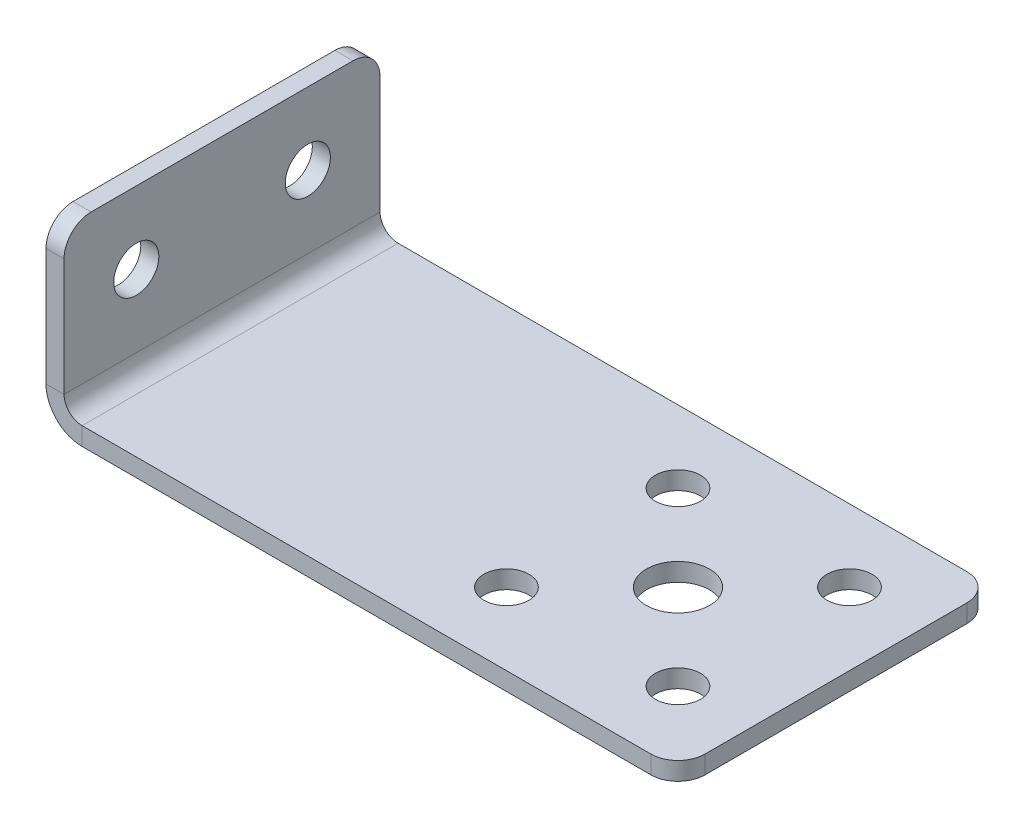
SolidWorks part; units mm, degrees
note: The reader was unsure of these and kept them because the rebuilt part matched: flange length of "Edge-Flange1".
ref_plane "Front Plane" through (0, 0, 0) normal (0, 0, 1) x (1, 0, 0)
ref_plane "Top Plane" through (0, 0, 0) normal (0, 1, 0) x (1, 0, 0)
ref_plane "Right Plane" through (0, 0, 0) normal (1, 0, 0) x (0, 0, -1)
sketch "Sketch1" plane through (0, 0, 0) normal (0, 1, 0) x (1, 0, 0)
  line L1 (35, -17.5) -> (-35, -17.5)
  line L2 (35, -17.5) -> (35, 17.5)
  line L3 (35, 17.5) -> (-35, 17.5)
  line L4 (-35, -17.5) -> (-35, 17.5)
  line L5 (35, -17.5) -> (-35, 17.5) construction
  line L6 (35, 17.5) -> (-35, -17.5) construction
  point P0 (0, 0)
  dimension "D1" = 70
  dimension "D2" = 35
base flange "Base-Flange1" sketch "Sketch1" thickness 2 reverse thickness direction yes parameters "D1"=9
edge flange "Edge-Flange1" sketch "Sketch8" flange angle 90 flange length 20 flange position material inside bend radius 2 thickness 2 relief rectangular parameters "D6"=10
sketch "Sketch8" plane through (-35, 2, 0) normal (1, 0, 0) x (0, 0, -1)
  line L2 (-17.5, 0) -> (-17.5, 18)
  line L3 (-17.5, 18) -> (17.5, 18)
  line L4 (17.5, 18) -> (17.5, 0)
  line L5 (17.5, 0) -> (-17.5, 0) construction
  line L6 (17.5, 0) -> (-17.5, 0)
bend "EdgeBend1" bend radius 2 bend angle 90 parameters "D5"=1
sketch "Sketch11" plane through (0, 2, 0) normal (0, 1, 0) x (1, 0, 0)
  line L0 (35, -17.5) -> (35, 17.5) construction
  line L1 (-31, -17.5) -> (35, -17.5) construction
  line L2 (35, 17.5) -> (-31, 17.5) construction
  point P0 (8, 9.5)
  point P2 (27, 9.5)
  point P4 (27, -9.5)
  point P6 (8, -9.5)
  dimension "D1" = 8
  dimension "D2" = 19
  dimension "D3" = 8
  dimension "D4" = 8
hole_wizard "Ø5.0mm Dowel Hole1" positions "Sketch11" profile "Sketch10" hole size "Ø5.0" standard "ISO" end condition through all
sketch "Sketch10" plane through (8, 2, -9.5) normal (1, 0, 0) x (0, 0, 1)
  line L0 (0, 0) -> (0, 2)
  line L1 (0, 2) -> (2.5, 2)
  line L2 (2.5, 2) -> (2.5, 0)
  line L5 (2.5, 0) -> (0, 0)
  line L11 (0, -6.35) -> (0, 107.95) construction
  dimension "Thru Hole Dia." = 5
  dimension "Thru Hole Depth" = 2
sketch "Sketch14" plane through (0, 2, 0) normal (0, 1, 0) x (1, 0, 0)
  circle A0 centre (27, -9.5) radius 2.5 construction
  circle A1 centre (27, 9.5) radius 2.5 construction
  point P0 (17.5, 0)
  dimension "D1" = 9.5
  dimension "D2" = 9.5
hole_wizard "Ø5.0mm Dowel Hole2" positions "Sketch14" profile "Sketch13" hole size "Ø5.0" standard "ISO" end condition through all
sketch "Sketch13" plane through (17.5, 2, 0) normal (1, 0, 0) x (0, 0, 1)
  line L0 (0, 0) -> (0, 2)
  line L1 (0, 2) -> (3.5, 2)
  line L2 (3.5, 2) -> (3.5, 0)
  line L5 (3.5, 0) -> (0, 0)
  line L11 (0, -6.35) -> (0, 107.95) construction
  dimension "Thru Hole Dia." = 7
  dimension "Thru Hole Depth" = 2
sketch "Sketch17" plane through (-33, 0, 0) normal (1, 0, 0) x (0, 0, -1)
  line L0 (17.5, 20) -> (-17.5, 20) construction
  line L1 (-9.5, 0) -> (-9.5, 2) construction
  line L2 (9.5, 0) -> (9.5, 2) construction
  point P0 (-9.5, 12)
  point P2 (9.5, 12)
  dimension "D1" = 8
hole_wizard "Ø5.0mm Dowel Hole3" positions "Sketch17" profile "Sketch16" hole size "Ø5.0" standard "ISO" end condition through all
sketch "Sketch16" plane through (-33, 12, 9.5) normal (0, 1, 0) x (0, 0, -1)
  line L0 (0, 0) -> (0, 2)
  line L1 (0, 2) -> (2.5, 2)
  line L2 (2.5, 2) -> (2.5, 0)
  line L5 (2.5, 0) -> (0, 0)
  line L11 (0, -6.35) -> (0, 107.95) construction
  dimension "Thru Hole Dia." = 5
  dimension "Thru Hole Depth" = 2
fillet "Fillet1" radius 3 4 edges at (35, 1, -17.5) (-34, 20, -17.5) (-34, 20, 17.5) (35, 1, 17.5)
sketch "Bend-Lines1" [suppressed] plane through (0, 0, 0) normal (0, 1, 0) x (1, 0, 0)
sketch "Bounding-Box1" [suppressed] plane through (0, 0, 0) normal (0, 1, 0) x (1, 0, 0)
sheet metal parameters "Sheet-Metal1" thickness 2 parameters "D1"=9
flat pattern "Flat-Pattern1" [suppressed]
sketch "Bend-Lines2" plane through (0, 0, 0) normal (0, 1, 0) x (1, 0, 0)
sketch3d "Bounding-Box2" [suppressed]
  line L0 (35, -17.5, 0) -> (-35, -17.5, 0) construction
  line L1 (35, 17.5, 0) -> (-35, 17.5, 0) construction
  line L2 (35, -17.5, 0) -> (35, 17.5, 0) construction
  line L3 (-35, -17.5, 0) -> (-35, 17.5, 0) construction
sheet metal parameters "Sheet-Metal2" thickness 2 parameters "D1"=9
flat pattern "Flat-Pattern1"
sketch "Bend-Lines2" plane through (0, 0, 0) normal (0, -1, 0) x (-1, 0, 0)
  line L0 (33.3562, -17.5) -> (33.3562, 17.5) construction
  line L1 (33.3562, -17.5) -> (33.3562, 17.5) construction
sketch3d "Bounding-Box2" [suppressed]
  line L0 (-35, -17.5, 0) -> (51.7124, -17.5, 0) construction
  line L1 (-35, 17.5, 0) -> (51.7124, 17.5, 0) construction
  line L2 (-35, -17.5, 0) -> (-35, 17.5, 0) construction
  line L3 (51.7124, -17.5, 0) -> (51.7124, 17.5, 0) construction
bend of the flat pattern "Flatten-<EdgeBend1>1"
sheet metal parameters "Sheet-Metal3" thickness 2 parameters "D1"=9
flat pattern "Flat-Pattern1"
sketch "Bend-Lines2" plane through (0, 0, 0) normal (0, -1, 0) x (-1, 0, 0)
  line L0 (33.3562, -17.5) -> (33.3562, 17.5) construction
  line L1 (33.3562, -17.5) -> (33.3562, 17.5) construction
sketch3d "Bounding-Box2" [suppressed]
  line L0 (-35, -17.5, 0) -> (51.7124, -17.5, 0) construction
  line L1 (-35, 17.5, 0) -> (51.7124, 17.5, 0) construction
  line L2 (-35, -17.5, 0) -> (-35, 17.5, 0) construction
  line L3 (51.7124, -17.5, 0) -> (51.7124, 17.5, 0) construction
bend of the flat pattern "Flatten-<EdgeBend1>1"
sheet metal parameters "Sheet-Metal4" thickness 2 parameters "D1"=9
flat pattern "Flat-Pattern1"
sketch "Bend-Lines2" plane through (0, 0, 0) normal (0, -1, 0) x (-1, 0, 0)
  line L0 (33.3562, -17.5) -> (33.3562, 17.5) construction
  line L1 (33.3562, -17.5) -> (33.3562, 17.5) construction
sketch3d "Bounding-Box2" [suppressed]
  line L0 (-35, -17.5, 0) -> (51.7124, -17.5, 0) construction
  line L1 (-35, 17.5, 0) -> (51.7124, 17.5, 0) construction
  line L2 (-35, -17.5, 0) -> (-35, 17.5, 0) construction
  line L3 (51.7124, -17.5, 0) -> (51.7124, 17.5, 0) construction
bend of the flat pattern "Flatten-<EdgeBend1>1"
sheet metal parameters "Sheet-Metal5" thickness 2 parameters "D1"=9
flat pattern "Flat-Pattern1"
sketch "Bend-Lines2" plane through (0, 0, 0) normal (0, -1, 0) x (-1, 0, 0)
  line L0 (33.3562, -17.5) -> (33.3562, 17.5) construction
  line L1 (33.3562, -17.5) -> (33.3562, 17.5) construction
sketch3d "Bounding-Box2" [suppressed]
  line L0 (-35, -17.5, 0) -> (51.7124, -17.5, 0) construction
  line L1 (-35, 17.5, 0) -> (51.7124, 17.5, 0) construction
  line L2 (-35, -17.5, 0) -> (-35, 17.5, 0) construction
  line L3 (51.7124, -17.5, 0) -> (51.7124, 17.5, 0) construction
bend of the flat pattern "Flatten-<EdgeBend1>1"
